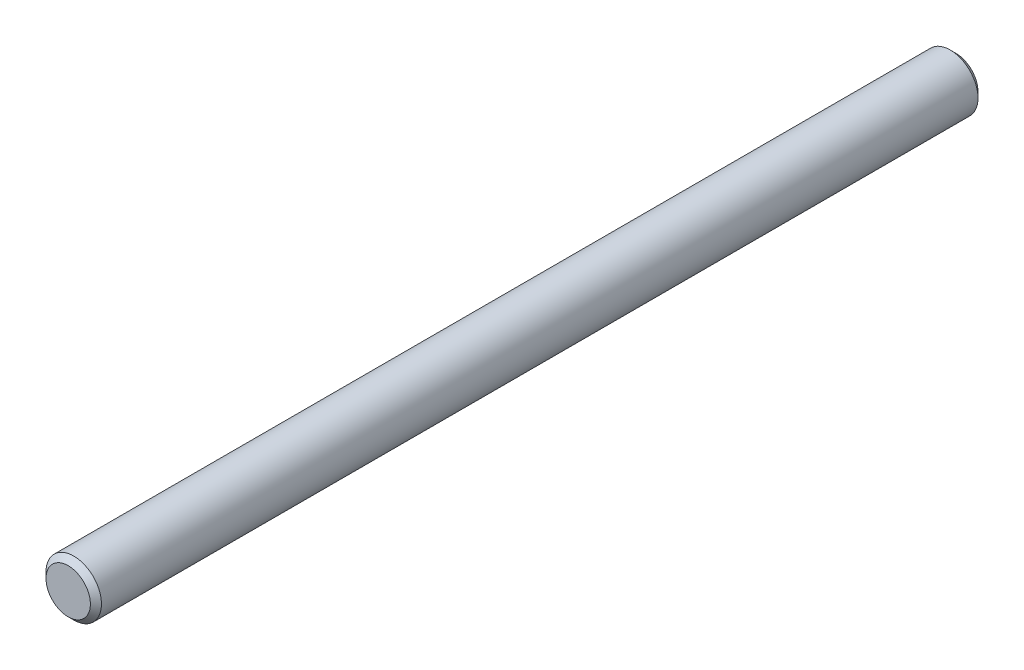
SolidWorks part; units mm, degrees
material "Plain Carbon Steel"
ref_plane "Front" through (0, 0, 0) normal (0, 0, 1) x (1, 0, 0)
ref_plane "Top" through (0, 0, 0) normal (0, 1, 0) x (1, 0, 0)
ref_plane "Right" through (0, 0, 0) normal (1, 0, 0) x (0, 0, -1)
sketch "Sketch1" plane through (0, 0, 0) normal (0, 0, 1) x (1, 0, 0)
  circle A0 centre (0, 0) radius 9.525
  dimension "dia" = 19.05
extrude "Extrude1" add sketch "Sketch1" along normal mid plane 304.8
sketch "Sketch2" plane through (0, 0, 0) normal (1, 0, 0) x (0, 0, -1)
  line L0 (152.4, 9.525) -> (149.86, 9.525) construction
  line L1 (152.4, 9.525) -> (-152.4, 9.525) construction
  line L2 (149.86, 9.525) -> (118.9037, 9.525) construction
  line L3 (118.9037, 9.525) -> (111.76, 9.525) construction
  line L4 (111.76, 9.525) -> (109.22, 9.525) construction
  line L5 (109.22, 9.525) -> (106.5632, 9.525) construction
  line L7 (97.6732, 9.525) -> (92.9107, 9.525) construction
  line L8 (92.9107, 9.525) -> (81.4807, 9.525) construction
  line L10 (-152.4, -9.525) -> (152.4, -9.525) construction
  line L11 (-152.4, 9.525) -> (-149.86, 9.525) construction
  line L12 (-149.86, 9.525) -> (-149.86, -9.525) construction
  line L13 (106.5632, 9.525) -> (97.6732, 9.525) construction
  line L14 (97.6732, 9.525) -> (97.6732, -9.525) construction
  line L15 (111.76, 9.525) -> (111.76, -9.525) construction
  line L16 (81.4807, 9.525) -> (76.7182, 9.525) construction
  line L17 (76.7182, 9.525) -> (65.2882, 9.525) construction
  line L18 (65.2882, 9.525) -> (60.5257, 9.525) construction
  line L19 (60.5257, 9.525) -> (49.0957, 9.525) construction
  line L20 (81.4807, 9.525) -> (81.4807, -9.525) construction
  line L21 (65.2882, 9.525) -> (65.2882, -9.525) construction
  line L22 (49.0957, 9.525) -> (49.0957, -9.525) construction
  line L23 (49.0957, 9.525) -> (44.3332, 9.525) construction
  line L24 (44.3332, 9.525) -> (32.9032, 9.525) construction
  line L25 (32.9032, 9.525) -> (32.9032, -9.525) construction
  line L26 (32.9032, 9.525) -> (28.1407, 9.525) construction
  line L27 (28.1407, 9.525) -> (16.7107, 9.525) construction
  line L28 (16.7107, 9.525) -> (11.9482, 9.525) construction
  line L29 (11.9482, 9.525) -> (0.5182, 9.525) construction
  line L30 (16.7107, 9.525) -> (16.7107, -9.525) construction
  line L31 (0.5182, 9.525) -> (0.5182, -9.525) construction
  line L32 (0.5182, 9.525) -> (-4.2443, 9.525) construction
  line L33 (-4.2443, 9.525) -> (-13.1343, 9.525) construction
  line L34 (-13.1343, 9.525) -> (-15.7912, 9.525) construction
  line L35 (-15.7912, 9.525) -> (-18.3312, 9.525) construction
  line L36 (-18.3312, 9.525) -> (-18.3312, -9.525) construction
  line L37 (-18.3312, 9.525) -> (-69.1312, 9.525) construction
  line L38 (-69.1312, 9.525) -> (-69.1312, -9.525) construction
  line L39 (109.22, 9.525) -> (109.22, -9.525) construction
  point P0 (-152.4, 9.525)
  point P1 (152.4, 9.525)
  dimension "D1" = 2.54
  dimension "D2" = 30.9562
  dimension "D3" = 7.1437
  dimension "D4" = 2.54
  dimension "D5" = 2.6568
  dimension "D6" = 8.89
  dimension "D7" = 11.43
  dimension "D8" = 2.54
  dimension "D9" = 4.7625
  dimension "D10" = 4.7625
  dimension "D11" = 11.43
  dimension "D12" = 4.7625
  dimension "D13" = 11.43
  dimension "D14" = 4.7625
  dimension "D15" = 11.43
  dimension "D16" = 4.7625
  dimension "D17" = 11.43
  dimension "D18" = 4.7625
  dimension "D19" = 11.43
  dimension "D20" = 4.7625
  dimension "D21" = 8.89
  dimension "D22" = 2.6568
  dimension "D23" = 2.54
  dimension "D24" = 50.8
chamfer "Chamfer1" distance 1.905 angle 45 2 edges at (9.525, 0, -152.4) (9.525, 0, 152.4)
equation "\"D1@Chamfer1\" = \"dia@Sketch1\" * .1"
